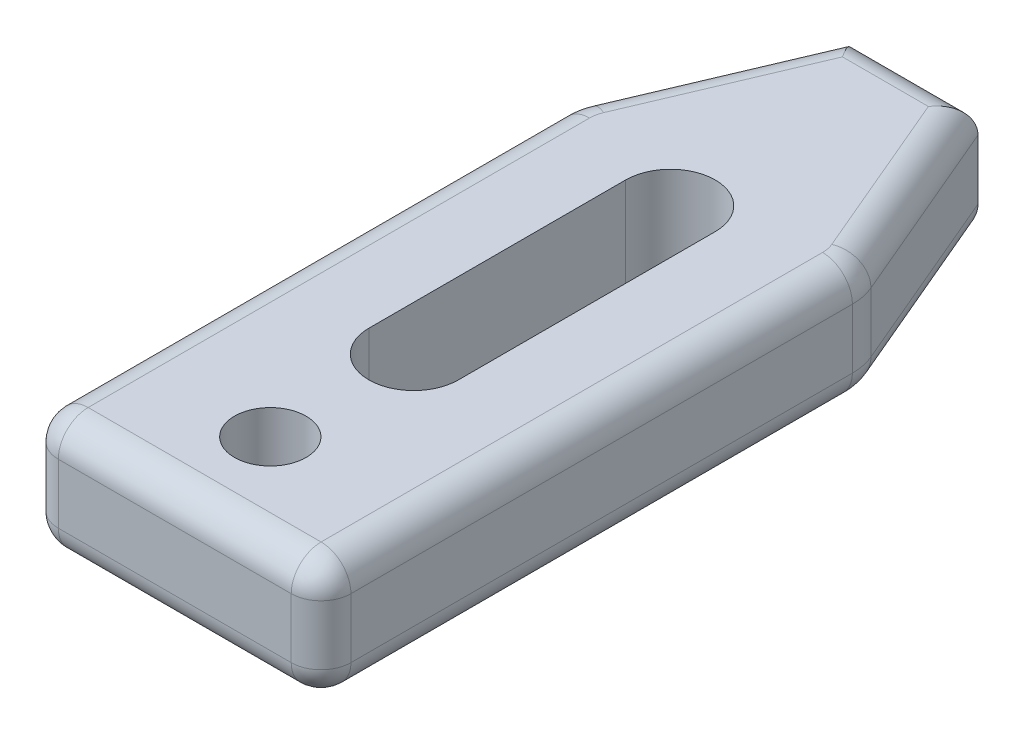
SolidWorks part; units mm, degrees
ref_plane "前视基准面" through (0, 0, 0) normal (0, 0, 1) x (1, 0, 0)
ref_plane "上视基准面" through (0, 0, 0) normal (0, 1, 0) x (1, 0, 0)
ref_plane "右视基准面" through (0, 0, 0) normal (1, 0, 0) x (0, 0, -1)
sketch "草图1" plane through (0, 0, 0) normal (0, 1, 0) x (1, 0, 0)
  line L1 (-24.5, -16) -> (24.5, -16)
  line L2 (-24.5, -16) -> (-24.5, 16)
  line L3 (-24.5, 16) -> (24.5, 16)
  line L4 (24.5, -16) -> (24.5, 16)
  line L5 (-24.5, -16) -> (24.5, 16) construction
  line L6 (-24.5, 16) -> (24.5, -16) construction
  circle A0 centre (0, 0) radius 6
  point P4 (0, 0)
  dimension "D3" = 12
  dimension "D1" = 49
  dimension "D2" = 32
extrude "凸台-拉伸1" add sketch "草图1" along normal blind 20
sketch "草图3" plane through (0, 0, 0) normal (0, 1, 0) x (1, 0, 0)
  line L0 (0, 67) -> (0, 24) construction
  line L1 (24.5, 16) -> (-24.5, 16)
  line L2 (24.5, 16) -> (24.5, 75)
  line L3 (24.5, 75) -> (-24.5, 75)
  line L4 (-24.5, 16) -> (-24.5, 75)
  line L5 (24.5, 16) -> (-24.5, 75) construction
  line L6 (24.5, 75) -> (-24.5, 16) construction
  line L7 (7.5, 67) -> (7.5, 24)
  line L8 (-7.5, 67) -> (-7.5, 24)
  line L9 (-10.5, 108) -> (10.5, 108)
  line L10 (0, 108) -> (0, 75) construction
  line L11 (-10.5, 108) -> (-24.5, 75)
  line L12 (10.5, 108) -> (24.5, 75)
  arc A0 (7.5, 67) -> (-7.5, 67) centre (0, 67) ccw
  arc A1 (-7.5, 24) -> (7.5, 24) centre (0, 24) ccw
  point P4 (0, 45.5)
  point P9 (0, 45.5)
  point P14 (0, 74.5)
  point P15 (0, 16.5)
  dimension "D2" = 7.5
  dimension "D3" = 58
  dimension "D1" = 59
  dimension "D4" = 21
  dimension "D5" = 33
extrude "凸台-拉伸2" add sketch "草图3" along normal blind 20 contours L4 L1 L2 L3 A1 L8 A0 L7 | L12 L9 L11 L3 region at (0, 0, -16.0767) region at (0, 0, -89.3)
fillet "圆角1" radius 10 2 edges at (24.5, 10, -75) (-24.5, 10, -75)
fillet "圆角2" radius 5 16 edges at (17.1029, 0, -92.436) (24.2994, 0, -74.9592) (-17.1029, 0, -92.436) (-24.2994, 0, -74.9592) (17.1029, 20, -92.436) (24.2994, 20, -74.9592) (-17.1029, 20, -92.436) (-24.2994, 20, -74.9592) (0, 20, -108) (0, 0, -108) (24.5, 0, -28.4833) (-24.5, 0, -28.4833) (24.5, 20, -28.4833) (-24.5, 20, -28.4833) (24.5, 10, 16) (-24.5, 10, 16)
fillet "圆角3" radius 5 3 edges at (-23.0355, 18.5355, 14.5355) (23.0355, 18.5355, 14.5355) (0, 20, 16)
fillet "圆角4" radius 5 3 edges at (-23.0355, 1.4645, 14.5355) (23.0355, 1.4645, 14.5355) (0, 0, 16)
ref_plane "基准面1" through (0, 0, -46) normal (0, 0, -1) x (-1, 0, 0)
